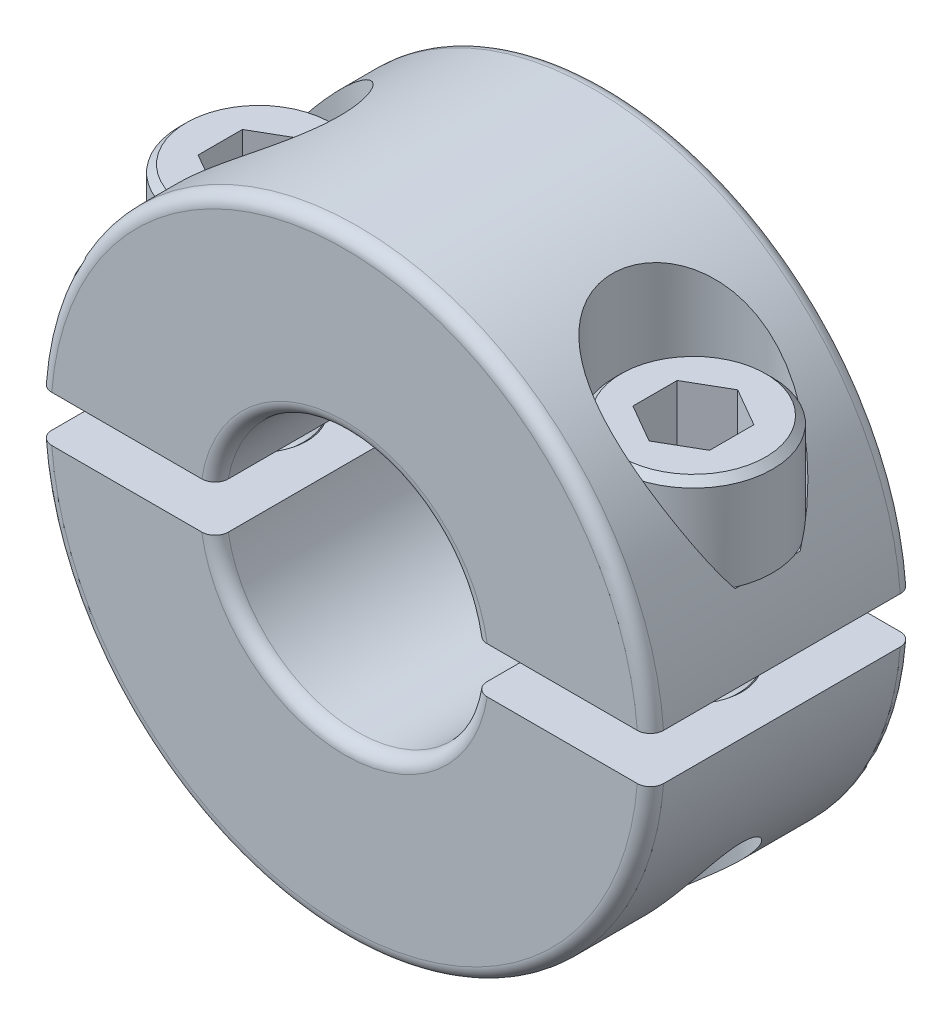
SolidWorks part; units mm, degrees
ref_plane "Front Plane" through (0, 0, 0) normal (0, 0, 1) x (1, 0, 0)
ref_plane "Top Plane" through (0, 0, 0) normal (0, 1, 0) x (1, 0, 0)
ref_plane "Right Plane" through (0, 0, 0) normal (1, 0, 0) x (0, 0, -1)
sketch "Sketch1" plane through (0, 0, 0) normal (0, 0, 1) x (1, 0, 0)
  line L0 (-11.1125, 0) -> (-4.7625, 0) construction
  line L1 (-11.0812, 0.8334) -> (-4.689, 0.8334)
  line L2 (-11.0812, -0.8334) -> (-4.689, -0.8334)
  line L3 (4.689, 0.8334) -> (11.0812, 0.8334)
  line L4 (4.689, -0.8334) -> (11.0812, -0.8334)
  line L5 (0, 0) -> (0, 11.1125) construction
  line L6 (-7.874, 0.8334) -> (-7.874, -0.8334) construction
  circle A0 centre (0, 0) radius 11.1125 construction
  circle A1 centre (0, 0) radius 4.7625 construction
  arc A4 (-4.689, -0.8334) -> (4.689, -0.8334) centre (0, 0) ccw
  arc A5 (-11.0812, -0.8334) -> (11.0812, -0.8334) centre (0, 0) ccw
  arc A6 (4.689, 0.8334) -> (-4.689, 0.8334) centre (0, 0) ccw
  arc A7 (11.0812, 0.8334) -> (-11.0812, 0.8334) centre (0, 0) ccw
  point P4 (11.1125, 0)
  point P14 (-11.1125, 0)
  point P18 (-7.874, 6.9675)
  point P19 (-4.7625, 0)
  point P21 (4.7625, 0)
  point P22 (-10.7442, 6.9675)
  point P23 (-10.7442, 3.4623)
  point P24 (-9.6266, -6.0627)
  point P26 (-9.6266, -5.2689)
  point P29 (-9.2631, 6.9675)
  dimension "OD" = 22.225
  dimension "Separation" = 1.6669
  dimension "Screw Center to Center" = 15.748
  dimension "Screw Size" = 3.5052
  dimension "Screw Head Height" = 3.5052
  dimension "Screw Head OD" = 5.7404
  dimension "Screw Thread Length" = 9.525
  dimension "D1" = 2.6289
  dimension "Hex" = 2.7781
  dimension "Pitch" = 0.7937
sketch "Sketch9" plane through (0, 0, 0) normal (1, 0, 0) x (0, 0, -1)
  line L0 (-4.7625, 0) -> (4.7625, 0) construction
  dimension "Width" = 9.525
sketch "Sketch10" plane through (0, 0, 0) normal (0, 0, 1) x (1, 0, 0)
  line L2 (-4.689, -0.8334) -> (-11.0812, -0.8334)
  line L3 (11.0812, -0.8334) -> (4.689, -0.8334)
  line L4 (-4.689, -0.8334) -> (-11.0812, -0.8334)
  line L5 (11.0812, -0.8334) -> (4.689, -0.8334)
  line L6 (-11.0812, 0.8334) -> (-4.689, 0.8334)
  line L7 (4.689, 0.8334) -> (11.0812, 0.8334)
  line L8 (-11.0812, 0.8334) -> (-4.689, 0.8334)
  line L9 (4.689, 0.8334) -> (11.0812, 0.8334)
  arc A2 (-4.689, -0.8334) -> (4.689, -0.8334) centre (0, 0) ccw
  arc A3 (-11.0812, -0.8334) -> (11.0812, -0.8334) centre (0, 0) ccw
  arc A4 (-4.689, -0.8334) -> (4.689, -0.8334) centre (0, 0) ccw
  arc A5 (-11.0812, -0.8334) -> (11.0812, -0.8334) centre (0, 0) ccw
  arc A6 (4.689, 0.8334) -> (-4.689, 0.8334) centre (0, 0) ccw
  arc A7 (11.0812, 0.8334) -> (-11.0812, 0.8334) centre (0, 0) ccw
  arc A8 (4.689, 0.8334) -> (-4.689, 0.8334) centre (0, 0) ccw
  arc A9 (11.0812, 0.8334) -> (-11.0812, 0.8334) centre (0, 0) ccw
  dimension "D1" = 0
  dimension "D2" = 0
extrude "Boss-Extrude1" add sketch "Sketch10" along normal mid plane 9.525 separate body
fillet "Fillet1" radius 0.4763 4 edges at (0, 4.7625, -4.7625) (0, 11.1125, -4.7625) (0, 4.7625, 4.7625) (0, 11.1125, 4.7625)
fillet "Fillet2" radius 0.4762 4 edges at (0, -11.1125, -4.7625) (0, -11.1125, 4.7625) (0, -4.7625, -4.7625) (0, -4.7625, 4.7625)
sketch "Sketch2" plane through (0, 0, 0) normal (0, 1, 0) x (1, 0, 0)
  line L0 (0, 4.7625) -> (0, -4.7625) construction
  line L1 (10.6035, 4.7625) -> (-10.6035, 4.7625) construction
  line L2 (-10.6035, -4.7625) -> (10.6035, -4.7625) construction
  line L3 (0, 0) -> (-4.7625, 0) construction
  line L4 (-4.7625, 0) -> (-11.1125, 0) construction
  line L7 (-7.9375, 4.7625) -> (-7.9375, -4.7625) construction
  line L8 (-8.128, 4.7625) -> (-7.747, 4.7625)
  line L10 (-11.1125, 0) -> (-4.7625, 0) construction
  arc A0 (-8.128, 4.7625) -> (-7.747, 4.7625) centre (-7.9375, 4.7625) ccw
  point P16 (-7.9375, 0)
  dimension "D2" = 0.1905
revolve "Cut-Revolve1" cut sketch "Sketch2" angle 360 about L0
sketch "Sketch3" plane through (0, 0, 0) normal (0, 0, 1) x (1, 0, 0)
  line L0 (-7.874, 11.1125) -> (-4.9403, 11.1125)
  line L1 (-4.9403, 11.1125) -> (-4.9403, 3.4623)
  line L2 (-4.9403, 3.4623) -> (-6.1214, 3.4623)
  line L3 (-6.1214, 3.4623) -> (-6.1214, -11.1125)
  line L4 (-6.1214, -11.1125) -> (-7.874, -11.1125)
  line L5 (-7.874, -11.1125) -> (-7.874, 11.1125)
  line L7 (-7.874, 11.1125) -> (-7.874, 14.0462) construction
  line L8 (-4.9403, 11.1125) -> (0, 11.1125) construction
  line L9 (0, -11.1125) -> (-6.1214, -11.1125) construction
  line L10 (-11.1125, 0) -> (-4.7625, 0) construction
  line L12 (0, 0) -> (0, -11.1125) construction
  line L14 (-7.874, 0.8334) -> (-7.874, -0.8334) construction
  circle A0 centre (0, 0) radius 11.1125 construction
  circle A2 centre (0, 0) radius 4.7625 construction
  arc A4 (-11.0812, -0.8334) -> (11.0812, -0.8334) centre (0, 0) ccw construction
  dimension "D1" = 5.8674
revolve "Cut-Revolve2" cut sketch "Sketch3" angle 360 about L5
mirror "Mirror1" about plane through (0, 0, 0) normal (1, 0, 0) of "Cut-Revolve2"
sketch "Sketch4" plane through (0, 0, 0) normal (0, 0, 1) x (1, 0, 0)
  line L0 (-7.874, 6.9675) -> (-5.0038, 6.9675)
  line L2 (-5.0038, 6.9675) -> (-5.0038, 3.4623)
  line L3 (-5.0038, 3.4623) -> (-6.1214, 3.4623)
  line L4 (-6.1214, 3.4623) -> (-6.1214, -6.0627)
  line L5 (-6.1214, 3.4623) -> (-6.1214, -11.1125) construction
  line L6 (-6.1214, -6.0627) -> (-7.874, -6.0627)
  line L7 (-7.874, -11.1125) -> (-7.874, 11.1125) construction
  line L8 (-7.874, -6.0627) -> (-7.874, 6.9675)
  line L9 (-6.1214, -6.0627) -> (-9.6266, -6.0627) construction
  line L10 (-7.874, 6.9675) -> (-7.874, 9.8377) construction
  dimension "Screw Lg" = 9.525
  dimension "Head Dia" = 5.7404
revolve "Revolve1" add sketch "Sketch4" angle 360 about L8
sketch "Sketch5" plane through (0, 6.9675, 0) normal (0, 1, 0) x (-1, 0, 0)
  line L1 (7.874, 1.604) -> (6.4849, 0.802)
  line L2 (6.4849, 0.802) -> (6.4849, -0.802)
  line L3 (6.4849, -0.802) -> (7.874, -1.604)
  line L4 (7.874, -1.604) -> (9.2631, -0.802)
  line L5 (9.2631, -0.802) -> (9.2631, 0.802)
  line L6 (9.2631, 0.802) -> (7.874, 1.604)
  circle A0 centre (7.874, 0) radius 1.3891 construction
  dimension "D1" = 2.7781
extrude "Cut-Extrude2" cut sketch "Sketch5" against normal blind 2.6289
chamfer "Chamfer3" distance 0.5953 angle 45 1 edges at (-7.874, -6.0627, -1.7526)
chamfer "Chamfer1" distance 0.254 angle 45 1 edges at (-7.874, 6.9675, -2.8702)
sketch "Sketch6" plane through (0, -6.0627, 0) normal (0, -1, 0) x (1, 0, 0)
  circle A0 centre (-7.874, 0) radius 1.7526 construction
  circle A1 centre (-7.874, 0) radius 1.7526
  point P3 (-9.6266, 0)
pattern_linear "LPattern2" count 2 spacing 15.748 along (1, 0, 0) of bodies 182
curve "Helix/Spiral1" pitch 0.7937 height 9.525 turns 12 parameters "Height"=9.525, "Pitch"=0.7937
sketch "Sketch7" plane through (0, 0, 0) normal (0, 0, 1) x (1, 0, 0)
  line L0 (-9.7125, -6.0131) -> (-9.7125, -6.8068) construction
  line L1 (-9.7125, -6.8068) -> (-9.0251, -6.4099) construction
  line L2 (-9.0251, -6.4099) -> (-9.7125, -6.0131) construction
  line L3 (-9.7125, -6.4099) -> (-9.6266, -6.4099) construction
  line L4 (-9.0251, -6.4099) -> (-9.111, -6.4099) construction
  line L5 (-9.111, -6.3603) -> (-9.111, -6.4595)
  line L6 (-9.6266, -6.7572) -> (-9.6266, -6.0627) construction
  line L7 (-9.111, -6.3603) -> (-9.6696, -6.0379)
  line L8 (-9.6696, -6.0379) -> (-9.6696, -6.782)
  line L9 (-9.6696, -6.782) -> (-9.111, -6.4595)
  point P10 (-9.6696, -6.4099)
  dimension "D1" = 0.7937
  dimension "D2" = 0.0992
sweep "Cut-Sweep1" cut profiles "Sketch7" path "Helix/Spiral1" align with end faces yes
pattern_linear "LPattern1" count 2 spacing 15.748 along (-1, 0, 0)
delete or keep bodies "Body-Delete/Keep 1" type delete bodies bodies 183
equation "\"D1@Sketch3\"=\"Screw Head OD@Sketch1\"+.005"
equation "\"D1@Cut-Extrude2\" = \"Screw Head Height@Sketch1\" * .750"
equation "\"Height@Helix/Spiral1\" = \"Screw Thread Length@Sketch1\""
equation "\"D1@Sketch7\" = \"Pitch@Sketch1\""
equation "\"D2@Sketch7\" = \"D1@Sketch7\"/8"
equation "\"D3@LPattern1\"=\"Screw Center to Center@Sketch1\""
equation "\"D1@Sketch1\"=\"Screw Size@Sketch1\"*0.75"
equation "\"D1@Boss-Extrude1\" = \"Width@Sketch9\""
equation "\"D1@Fillet1\" = \"Width@Sketch9\" * .05"
equation "\"D1@Fillet2\"=\"D1@Fillet1\""
equation "\"Screw Dia@Sketch3\"=\"Screw Size@Sketch1\""
equation "\"Head Ht@Sketch4\"=\"Screw Head Height@Sketch1\""
equation "\"Screw Lg@Sketch4\"=\"Screw Thread Length@Sketch1\""
equation "\"Head Dia@Sketch4\"=\"Screw Head OD@Sketch1\""
equation "\"D1@Sketch5\" = \"Hex@Sketch1\""
equation "\"D1@Chamfer3\" = \"Pitch@Sketch1\" * 0.75"
equation "\"D3@LPattern2\" = \"Screw Center to Center@Sketch1\""
equation "\"Pitch@Helix/Spiral1\" = \"Pitch@Sketch1\""
